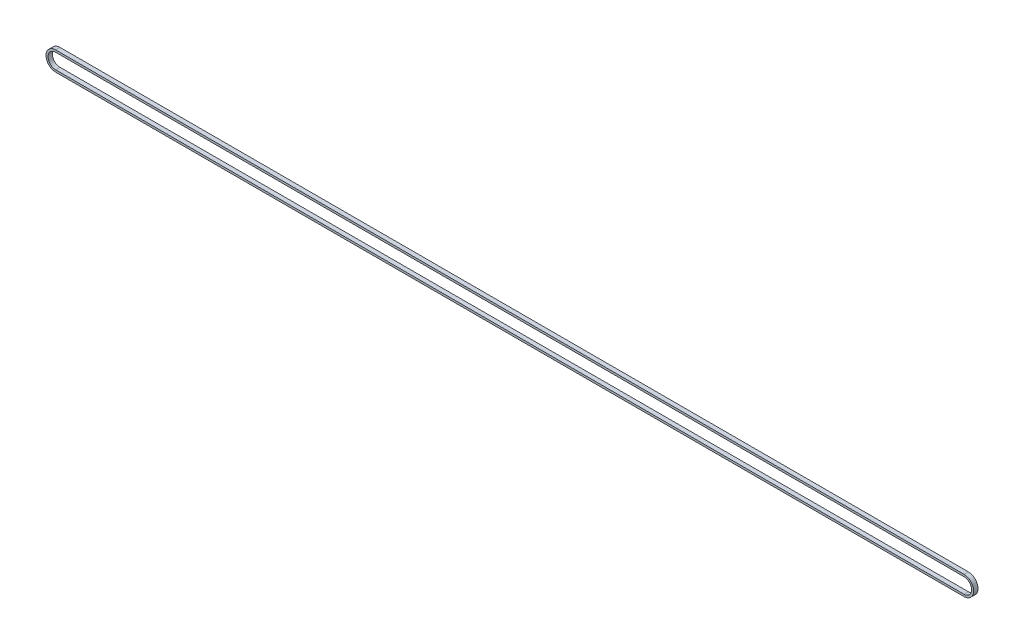
SolidWorks part; units mm, degrees
material "Rubber"
ref_plane "Front Plane" through (0, 0, 0) normal (0, 0, 1) x (1, 0, 0)
ref_plane "Top Plane" through (0, 0, 0) normal (0, 1, 0) x (1, 0, 0)
ref_plane "Right Plane" through (0, 0, 0) normal (1, 0, 0) x (0, 0, -1)
sketch "Sketch1" plane through (0, 0, 0) normal (0, 0, 1) x (1, 0, 0)
  line L0 (0, 0) -> (1047.8, 0) construction
  line L1 (0, 8.75) -> (1047.8, 8.75)
  line L2 (1047.8, -8.75) -> (0, -8.75)
  arc A0 (0, 8.75) -> (0, -8.75) centre (0, 0) ccw
  arc A1 (1047.8, -8.75) -> (1047.8, 8.75) centre (1047.8, 0) ccw
  dimension "D1" = 17.5
  dimension "D2" = 1047.8
extrude "Extrude-Thin1" add sketch "Sketch1" along normal mid plane 5 thin thin type one direction wall 2.4
